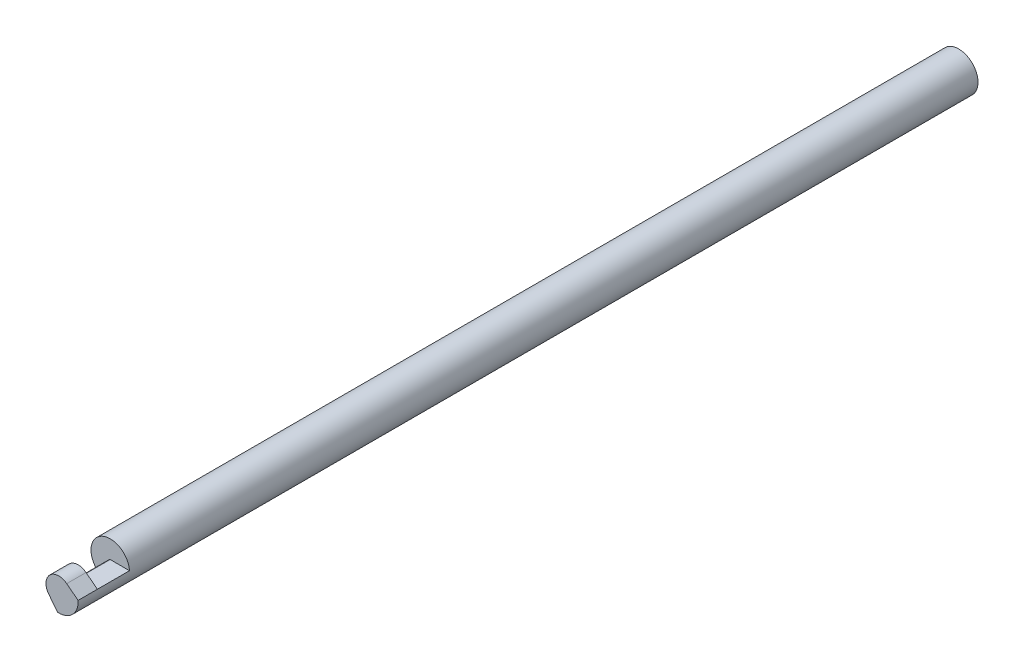
SolidWorks part; units mm, degrees
material "AISI 316 Annealed Stainless Steel Bar (SS)"
ref_plane "Front" through (0, 0, 0) normal (0, 0, 1) x (1, 0, 0)
ref_plane "Top" through (0, 0, 0) normal (0, 1, 0) x (1, 0, 0)
ref_plane "Right" through (0, 0, 0) normal (1, 0, 0) x (0, 0, -1)
ref_axis "X" through (-80.9, 0, 0) along (1, 0, 0)
ref_axis "Y" through (0, -50, 0) along (0, 1, 0)
ref_axis "Z" through (0, 0, -80.9) along (0, 0, 1)
sketch "Sketch1" plane through (0, 0, 0) normal (1, 0, 0) x (0, 0, -1)
  line L0 (0, 0) -> (0, 1.5)
  line L1 (0, 1.5) -> (70, 1.5)
  line L2 (70, 1.5) -> (70, 0)
  line L3 (70, 0) -> (0, 0)
  line L4 (-9.841, 0) -> (-3.2015, 0) construction
  dimension "D1" = 3
  dimension "D2" = 70
revolve "Revolve1" add sketch "Sketch1" angle 360 about L4
sketch "Sketch2" plane through (0, 0, 0) normal (0, 0, 1) x (1, 0, 0)
  line L0 (0, 0.1) -> (1.4967, 0.1)
  line L1 (-0.1, 0) -> (-0.1, -1.4967)
  arc A0 (0, 0.1) -> (-0.1, 0) centre (0, 0) ccw
  circle A2 centre (0, 0) radius 1.5
  arc A3 (1.4967, 0.1) -> (-0.1, -1.4967) centre (0, 0) ccw
  dimension "D2" = 0.1
  dimension "D1" = 0
extrude "Cut-Extrude1" cut sketch "Sketch2" against normal blind 2.5 from offset 1.5 offset against normal yes
sketch "Sketch3" plane through (0, 0, 0) normal (0, 0, 1) x (1, 0, 0)
  line L0 (1.4967, 0.1) -> (0.6155, 0.7881)
  line L1 (-0.1, -1.4967) -> (-0.7881, -0.6155)
  arc A0 (0.6155, 0.7881) -> (-0.7881, -0.6155) centre (0, 0) ccw
  circle A2 centre (0, 0) radius 1.5 construction
  arc A3 (1.4967, 0.1) -> (-0.1, -1.4967) centre (0, 0) ccw
  point P1 (-0.8851, -0.1112)
  point P3 (-0.1, -1.4967)
  dimension "D1" = 1
extrude "Cut-Extrude2" cut sketch "Sketch3" against normal up to surface (1.5 mm away) up to face at (-0.1208, 0.1208, -1.5)
